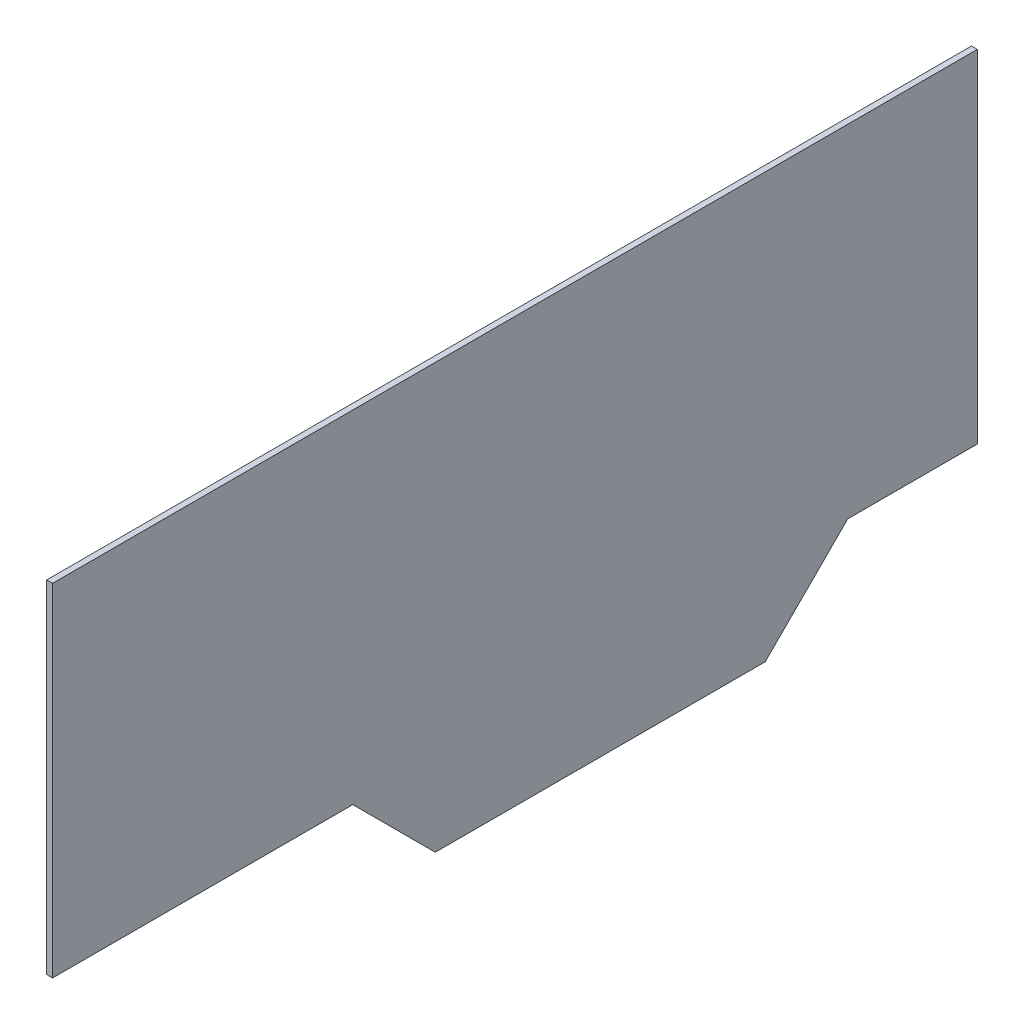
SolidWorks part; units mm, degrees
material "6061-T6 (SS)"
ref_plane "X-Y Datum" through (0, 0, 0) normal (0, 0, 1) x (1, 0, 0)
ref_plane "X-Z Datum" through (0, 0, 0) normal (0, 1, 0) x (1, 0, 0)
ref_plane "Y-Z Datum" through (0, 0, 0) normal (1, 0, 0) x (0, 0, -1)
sketch "Sketch1" plane through (0, 0, 0) normal (1, 0, 0) x (0, 0, -1)
  line L1 (-249.174, 88.9) -> (249.174, 88.9)
  line L2 (-249.174, 88.9) -> (-249.174, -88.9)
  line L3 (-249.174, -88.9) -> (249.174, -88.9)
  line L4 (249.174, 88.9) -> (249.174, -88.9)
  line L5 (-249.174, 88.9) -> (249.174, -88.9) construction
  line L6 (-249.174, -88.9) -> (249.174, 88.9) construction
  point P0 (0, 0)
  dimension "D1" = 177.8
  dimension "D2" = 498.348
extrude "Boss-Extrude1" add sketch "Sketch1" along normal mid plane 3.175
sketch "Sketch2" plane through (1.5875, 0, 0) normal (1, 0, 0) x (0, 0, -1)
  line L0 (249.174, -88.9) -> (249.174, -95.25)
  line L1 (249.174, -95.25) -> (179.324, -95.25)
  line L2 (179.324, -95.25) -> (134.874, -139.7)
  line L3 (134.874, -139.7) -> (-42.926, -139.7)
  line L5 (-249.174, -88.9) -> (249.174, -88.9) construction
  line L6 (-249.174, -88.9) -> (249.174, -88.9)
  line L7 (-249.174, -88.9) -> (-249.174, -95.25)
  line L8 (-249.174, -95.25) -> (-87.376, -95.25)
  line L9 (-87.376, -95.25) -> (-42.926, -139.7)
  line L10 (249.174, -88.9) -> (249.174, 88.9) construction
  line L11 (-249.174, -88.9) -> (249.174, -88.9) construction
  line M10 (-249.174, -88.9) -> (249.174, -88.9)
  dimension "D1" = 6.35
  dimension "D2" = 69.85
  dimension "D3" = 177.8
  dimension "D4" = 135
  dimension "D5" = 6.35
  dimension "D6" = 135
  dimension "D7" = 50.8
extrude "Boss-Extrude2" add sketch "Sketch2" against normal blind 3.175 contours L3 L2 L1 L0 M10 region at (1.5875, -110.1905, -34.8202)
